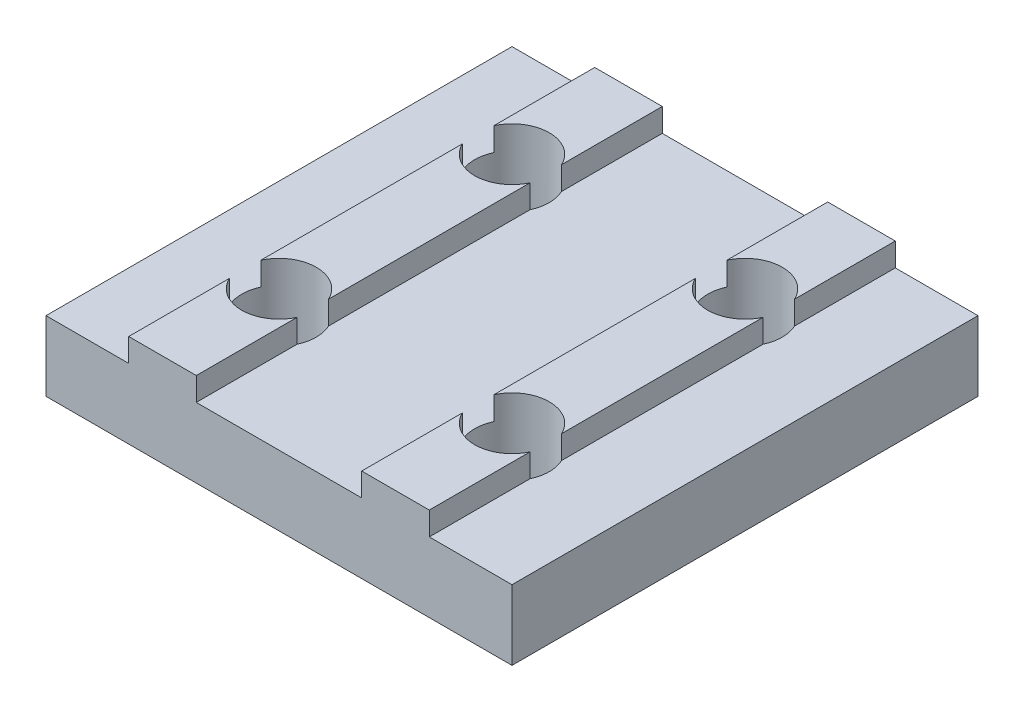
SolidWorks part; units mm, degrees
ref_plane "Front Plane" through (0, 0, 0) normal (0, 0, 1) x (1, 0, 0)
ref_plane "Top Plane" through (0, 0, 0) normal (0, 1, 0) x (1, 0, 0)
ref_plane "Right Plane" through (0, 0, 0) normal (1, 0, 0) x (0, 0, -1)
sketch "Esquisse1" plane through (0, 0, 0) normal (0, 0, 1) x (1, 0, 0)
  line L0 (-5, 0) -> (-5, 3)
  line L1 (-5, 3) -> (-1.45, 3)
  line L2 (-1.45, 3) -> (-1.45, 4)
  line L3 (-1.45, 4) -> (1.45, 4)
  line L4 (1.45, 4) -> (1.45, 3)
  line L5 (1.45, 3) -> (5, 3)
  line L6 (5, 3) -> (5, 0)
  line L7 (5, 0) -> (-5, 0)
  point P11 (0, 0)
  dimension "D1" = 10
  dimension "D2" = 3
  dimension "D3" = 1
  dimension "D4" = 2.9
  dimension "D5" = 3.55
extrude "Main" add sketch "Esquisse1" along normal blind 20
sketch "Esquisse2" plane through (0, 4, 0) normal (0, 1, 0) x (1, 0, 0)
  line L0 (0, -2.2) -> (0, 2.2) construction
  line L1 (-1.45, 0) -> (-5, 0) construction
  line L2 (-1.45, -20) -> (-5, -20) construction
  circle A0 centre (0, -5) radius 1.6
  circle A1 centre (0, -15) radius 1.6
  dimension "D2" = 5
  dimension "D3" = 3.2
  dimension "D1" = 5
extrude "TopHole" cut sketch "Esquisse2" against normal through all
ref_axis "Axe1" through (-5.5, 0, 0) along (1, 0, 0)
pattern_linear "Répétition linéaire1" count 2 spacing 10 along (-1, 0, 0) of "TopHole", "Main"
